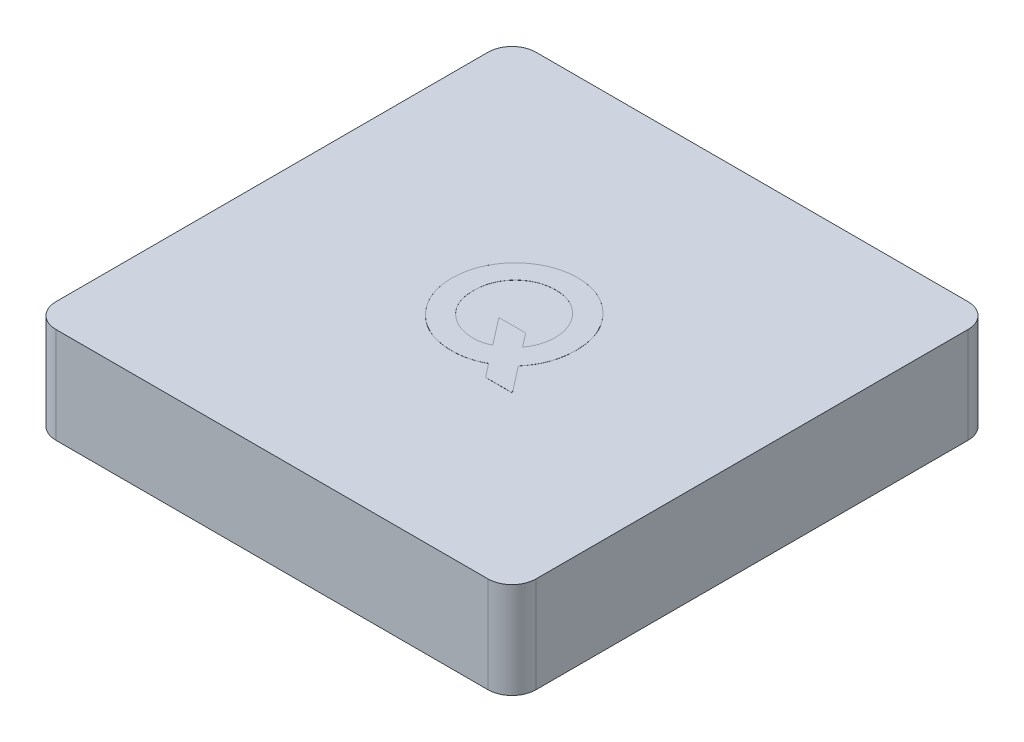
SolidWorks part; units mm, degrees
ref_plane "Front Plane" through (0, 0, 0) normal (0, 0, 1) x (1, 0, 0)
ref_plane "Top Plane" through (0, 0, 0) normal (0, 1, 0) x (1, 0, 0)
ref_plane "Right Plane" through (0, 0, 0) normal (1, 0, 0) x (0, 0, -1)
sketch "Sketch1" plane through (0, 0, 0) normal (0, 1, 0) x (1, 0, 0)
  line L0 (0, 0) -> (12.7, 0)
  line L1 (12.7, 0) -> (12.7, 12.7)
  line L2 (12.7, 12.7) -> (0, 12.7)
  line L3 (0, 12.7) -> (0, 0)
  dimension "D1" = 12.7
  dimension "D2" = 12.7
extrude "Boss-Extrude1" add sketch "Sketch1" along normal blind 2.54
fillet "Fillet1" radius 0.635 4 edges at (0, 1.27, -12.7) (12.7, 1.27, -12.7) (12.7, 1.27, 0) (0, 1.27, 0)
shell "Shell1" thickness 0.635 removed face at (6.35, 0, -6.35)
sketch "Sketch2" plane through (0, 1.905, 0) normal (0, -1, 0) x (-1, 0, 0)
  line L0 (-0.635, 6.35) -> (-12.065, 6.35) construction
  line L1 (-0.635, 12.065) -> (-0.635, 0.635) construction
  line L2 (-12.065, 0.635) -> (-12.065, 12.065) construction
  line L3 (-6.35, 0.635) -> (-6.35, 12.065) construction
  line L4 (-0.635, 0.635) -> (-12.065, 0.635) construction
  line L5 (-12.065, 12.065) -> (-0.635, 12.065) construction
  circle A0 centre (-6.35, 6.35) radius 2.54
  dimension "D1" = 5.08
extrude "Boss-Extrude2" add sketch "Sketch2" along normal up to surface (1.905 mm away) up to face at (6.35, 0, -6.35)
sketch "Sketch3" plane through (0, 2.54, 0) normal (0, 1, 0) x (1, 0, 0)
  line L0 (0, 12.065) -> (0, 0.635) construction
  line L1 (0.635, 0) -> (12.065, 0) construction
  text T0 "<b>Q</b>"
  point P1 (0, 0)
  dimension "D1" = 4.4958
  dimension "D2" = 4.826
extrude "Boss-Extrude3" add sketch "Sketch3" along normal blind 0.0025
